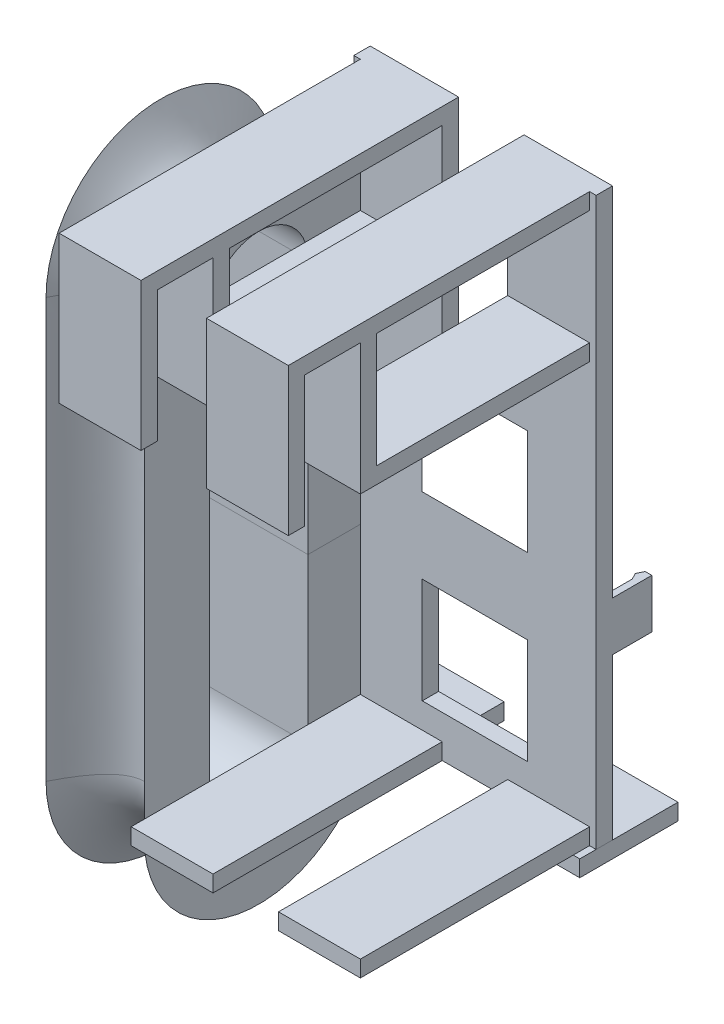
SolidWorks part; units mm, degrees
ref_plane "Front Plane" through (0, 0, 0) normal (0, 0, 1) x (1, 0, 0)
ref_plane "Top Plane" through (0, 0, 0) normal (0, 1, 0) x (1, 0, 0)
ref_plane "Right Plane" through (0, 0, 0) normal (1, 0, 0) x (0, 0, -1)
sketch "Sketch1" plane through (0, 0, 0) normal (0, 0, 1) x (1, 0, 0)
  line L0 (35, 87.5) -> (35, 113) construction
  line L1 (0, 0) -> (70, 0)
  line L2 (0, 0) -> (0, 113)
  line L3 (0, 113) -> (70, 113)
  line L4 (70, 0) -> (70, 113)
  line L5 (0, 113) -> (25, 113)
  line L6 (0, 113) -> (0, 173)
  line L7 (0, 173) -> (25, 173)
  line L8 (25, 113) -> (25, 173)
  line L9 (70, 113) -> (45, 113)
  line L10 (70, 113) -> (70, 173)
  line L11 (70, 173) -> (45, 173)
  line L12 (45, 113) -> (45, 173)
  line L13 (0, 56.5) -> (70, 56.5) construction
  line L14 (18.9, 68.05) -> (51.1, 68.05)
  line L15 (18.9, 68.05) -> (18.9, 100.25)
  line L16 (18.9, 100.25) -> (51.1, 100.25)
  line L17 (51.1, 68.05) -> (51.1, 100.25)
  line L18 (18.9, 12.75) -> (51.1, 12.75)
  line L19 (51.1, 44.95) -> (51.1, 12.75)
  line L20 (18.9, 44.95) -> (51.1, 44.95)
  line L21 (18.9, 44.95) -> (18.9, 12.75)
  line L23 (0, 173) -> (-2, 173)
  line L24 (0, 173) -> (0, 0)
  line L25 (0, 0) -> (-2, 0)
  line L26 (-2, 173) -> (-2, 0)
  line L27 (70, 0) -> (72, 0)
  line L28 (70, 0) -> (70, 173)
  line L29 (70, 173) -> (72, 173)
  line L30 (72, 0) -> (72, 173)
  point P11 (35, 87.5)
  point P21 (35, 100.25)
  dimension "D1" = 70
  dimension "D2" = 113
  dimension "D3" = 60
  dimension "D4" = 25.5
  dimension "D5" = 32.2
  dimension "D6" = 25
  dimension "D7" = 2
extrude "Boss-Extrude1" add sketch "Sketch1" along normal blind 5 contours L3 L8 L7 L6 | L12 L3 L10 L11 | L1 L4 L3 L2 L21 L20 L19 L18 L17 L14 L15 L16 | L23 L26 L25 L2 L6 | L27 L30 L29 L10 L4 region at (35, 56.5, 0) region at (-1, 86.5, 0) region at (71, 86.5, 0) region at (12.5, 143, 0) region at (57.5, 143, 0)
sketch "Sketch2" plane through (0, 0, 0) normal (1, 0, 0) x (0, 0, -1)
  line L1 (-5, 173) -> (-97, 173)
  line L2 (-5, 173) -> (-5, 168)
  line L3 (-5, 168) -> (-97, 168)
  line L4 (-97, 173) -> (-97, 168)
  line L5 (-97, 168) -> (-92, 168)
  line L6 (-97, 168) -> (-97, 128)
  line L7 (-97, 128) -> (-92, 128)
  line L8 (-92, 168) -> (-92, 128)
  line L10 (-75, 168) -> (-70, 168)
  line L11 (-75, 168) -> (-75, 128)
  line L12 (-75, 128) -> (-70, 128)
  line L13 (-70, 168) -> (-70, 128)
  line L14 (-5, 173) -> (-5, 0) construction
  line L15 (-70, 128) -> (-5, 128)
  line L16 (-70, 128) -> (-70, 133)
  line L17 (-70, 133) -> (-5, 133)
  line L18 (-5, 128) -> (-5, 133)
  line L19 (-5, 0) -> (-75, 0)
  line L20 (-5, 0) -> (-5, 5)
  line L21 (-5, 5) -> (-75, 5)
  line L22 (-75, 0) -> (-75, 5)
  dimension "D1" = 5
  dimension "D2" = 40
  dimension "D3" = 17
  dimension "D5" = 5
  dimension "D4" = 70
extrude "Boss-Extrude2" add sketch "Sketch2" along normal blind 25 contours L15 L18 L17 L13 | L13 L3 L11 L12 | L8 L3 L6 L7 | L1 L4 L3 L2 | L22 L19 L20 L21 region at (0, 170.5, 51) region at (0, 148, 94.5) region at (0, 148, 72.5) region at (0, 130.5, 37.5) region at (0, 2.5, 40)
ref_plane "Mid Pane" through (35, 0, 0) normal (1, 0, 0) x (0, 0, -1)
mirror "Mirror2" about plane through (35, 0, 0) normal (1, 0, 0) of "Boss-Extrude2"
sketch "Sketch3" plane through (0, 0, 0) normal (1, 0, 0) x (0, 0, -1)
  line L0 (0, 64) -> (0, 49)
  line L1 (0, 0) -> (0, 173) construction
  line L2 (-5, 0) -> (0, 0) construction
  line L3 (0, 49) -> (12, 49)
  line L4 (12, 49) -> (12, 64)
  line L5 (12, 64) -> (0, 64)
  point P5 (0, 56.5)
  point P8 (-2.5, 0)
  dimension "D1" = 56.5
  dimension "D2" = 15
  dimension "D3" = 12
extrude "Boss-Extrude3" add sketch "Sketch3" against normal through all
sketch "Sketch4" plane through (0, 64, 0) normal (0, 1, 0) x (1, 0, 0)
  line L0 (0, 12) -> (1, 10)
  line L1 (1, 10) -> (0, 10)
  line L2 (0, 12) -> (0, 0) construction
  line L3 (0, 8) -> (0, 12)
  line L4 (0, 8) -> (1, 10)
  line M7 (0, 0) -> (0, 12)
  dimension "D1" = 2
  dimension "D2" = 1
extrude "Boss-Extrude5" add sketch "Sketch4" against normal up to surface (15 mm away) contours L1 L0 M7 | L4 L1 M7 region at (0.3333, 64, -10.6667) region at (0.3333, 64, -9.3333) up to face at (-1, 49, -6)
mirror "Mirror3" about plane through (35, 0, 0) normal (1, 0, 0) of "Boss-Extrude5", "Boss-Extrude3"
sketch "Sketch5" plane through (0, 0, 0) normal (0, 0, -1) x (-1, 0, 0)
  line L0 (-72, 0) -> (2, 0) construction
  line L1 (-72, 0) -> (-51.1, 0)
  line L2 (-72, 0) -> (-72, -5)
  line L3 (-72, -5) -> (-51.1, -5)
  line L4 (-51.1, 0) -> (-51.1, -5)
  line L7 (-72, 0) -> (-72, 49) construction
  line L8 (-51.1, 44.95) -> (-51.1, 12.75) construction
  line L9 (-18.9, 0) -> (2, 0)
  line L10 (-18.9, 0) -> (-18.9, -5)
  line L11 (-18.9, -5) -> (2, -5)
  line L12 (2, 0) -> (2, -5)
  line L13 (-18.9, 44.95) -> (-18.9, 12.75) construction
  dimension "D1" = 5
extrude "Boss-Extrude6" add sketch "Sketch5" along normal blind 20 and the other way blind 10 separate body
fillet "Fillet1" radius 2 2 edges at (0, 56.5, 0) (70, 56.5, 0)
sketch "Sketch7" plane through (0, 0, 0) normal (-1, 0, 0) x (0, 0, 1)
  line L0 (36, 128) -> (36, 0) construction
  line L1 (51, 128) -> (51, 0)
  line L2 (21, 128) -> (21, 0)
  line L7 (5, 173) -> (5, 0) construction
  line L9 (75, 128) -> (5, 128) construction
  line L10 (5, 0) -> (75, 0) construction
  arc A0 (51, 128) -> (21, 128) centre (36, 128) ccw
  arc A1 (21, 0) -> (51, 0) centre (36, 0) ccw
  point P2 (36, 64)
  dimension "D1" = 30
  dimension "D2" = 16
ref_plane "Plane2" through (0, 50, 0) normal (0, 1, 0) x (1, 0, 0)
sketch "Sketch8" plane through (0, 50, 0) normal (0, 1, 0) x (1, 0, 0)
  line L0 (0, -21) -> (-30, -21)
  line L1 (0, -21) -> (0, -1)
  line L2 (-30, -21) -> (-30, -1)
  line L3 (-15, -21) -> (-15, -16) construction
  spline S0 degree 2 poles (-30, -1) (-15, -31) (0, -1) knots 0 0 0 1 1 1
  dimension "D1" = 30
  dimension "D2" = 5
  dimension "D3" = 20
sweep "Sweep5" add profiles "Sketch8" path "Sketch7"
chamfer "Chamfer1" distance 5 angle 45 4 edges at (51.1, 84.15, 0) (35, 100.25, 0) (18.9, 84.15, 0) (35, 68.05, 0)
equation "\"plateThickness\"=0.005"
equation "\"D1@Boss-Extrude1\"=\"plateThickness\""
equation "\"D1@Sketch2\"=\"plateThickness\""
equation "\"D5@Sketch2\"=\"plateThickness\""
equation "\"D1@Sketch5\"=\"plateThickness\""
equation "\"D2@Boss-Extrude6\"=\"plateThickness\""
